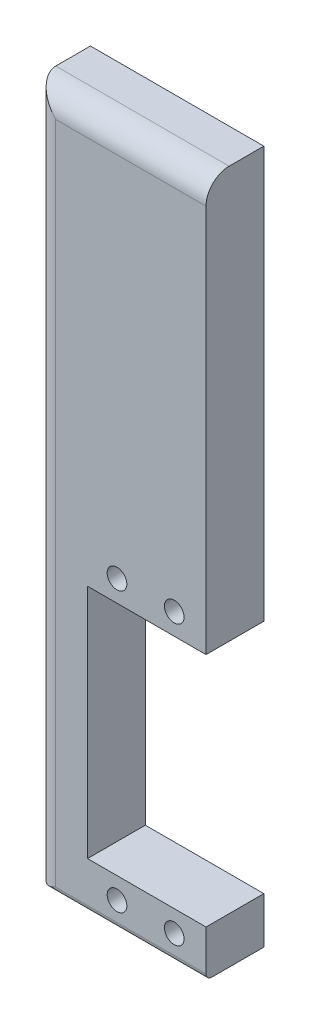
SolidWorks part; units mm, degrees
ref_plane "Front Plane" through (0, 0, 0) normal (0, 0, 1) x (1, 0, 0)
ref_plane "Top Plane" through (0, 0, 0) normal (0, 1, 0) x (1, 0, 0)
ref_plane "Right Plane" through (0, 0, 0) normal (1, 0, 0) x (0, 0, -1)
sketch "Sketch2" plane through (0, 0, 0) normal (0, 0, 1) x (1, 0, 0)
  line L1 (-30.9917, 52.1901) -> (-0.9917, 52.1901)
  line L2 (-30.9917, 52.1901) -> (-30.9917, -67.8099)
  line L3 (-30.9917, -67.8099) -> (-0.9917, -67.8099)
  line L4 (-0.9917, 52.1901) -> (-0.9917, -67.8099)
  dimension "D1" = 120
  dimension "D2" = 30
extrude "Boss-Extrude1" add sketch "Sketch2" along normal blind 10
sketch "Sketch3" plane through (0, 0, 0) normal (0, 0, 1) x (1, 0, 0)
  line L0 (-21.4917, -39.3862) -> (-0.9917, -39.3862) construction
  line L1 (-0.9917, -18.9862) -> (-0.9917, -59.7862)
  line L3 (-0.9917, -67.8099) -> (-0.9917, 52.1901) construction
  line L4 (-21.4917, -59.7862) -> (-21.4917, -63.4862) construction
  line L7 (-0.9917, -59.7862) -> (-21.4917, -59.7862)
  line L9 (-21.4917, -63.4862) -> (-16.3917, -63.4862) construction
  line L10 (-0.9917, -59.7862) -> (-0.9917, -63.4862) construction
  line L11 (-0.9917, -63.4862) -> (-6.4917, -63.4862) construction
  line L12 (-21.4917, -18.9862) -> (-21.4917, -59.7862)
  line L13 (-21.4917, -18.9862) -> (-0.9917, -18.9862)
  line L14 (-0.9917, -18.9862) -> (-0.9917, -59.7862)
  circle A0 centre (-16.3917, -63.4862) radius 1.7
  circle A1 centre (-6.4917, -63.4862) radius 1.7
  circle A2 centre (-6.4917, -15.2862) radius 1.7
  circle A3 centre (-16.3917, -15.2862) radius 1.7
  point P18 (-17.391, -63.1065)
  point P19 (-21.4917, -63.7945)
  point P20 (0, 0)
  point P21 (0, 0)
  point P22 (-21.4917, -63.4505)
  point P23 (-17.1408, -63.4818)
  point P24 (-5.3188, -63.732)
  dimension "D3" = 5.1
  dimension "D1" = 40.8
  dimension "D2" = 20.5
  dimension "D4" = 3.7
  dimension "D5" = 5.5
  dimension "D6" = 3.7
extrude "Cut-Extrude3" cut sketch "Sketch3" along normal through all contours A1 | A0 | A2 | L13 L1 L7 L12 | A3
fillet "Fillet1" radius 1 1 edges at (-15.9917, -67.8099, 10) type face fillet first side face at (-14.6917, -63.4862, 10) second side face at (-15.9917, -67.8099, 5)
fillet "Fillet2" radius 4 3 edges at (-15.9917, 52.1901, 10) (-30.9917, -7.3099, 10) (-30.9917, -67.517, 9.7071)
